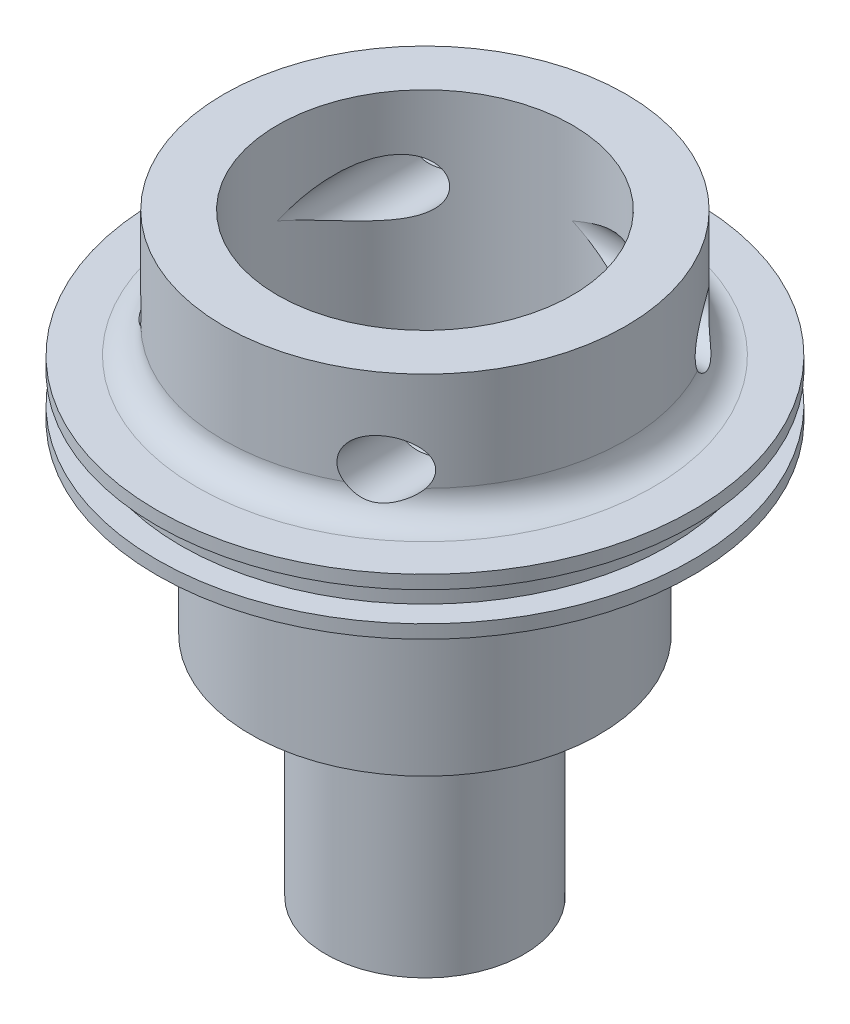
SolidWorks part; units mm, degrees
material "AISI 316 Stainless Steel Sheet (SS)"
ref_plane "Front Plane" through (0, 0, 0) normal (0, 0, 1) x (1, 0, 0)
ref_plane "Top Plane" through (0, 0, 0) normal (0, 1, 0) x (1, 0, 0)
ref_plane "Right Plane" through (0, 0, 0) normal (1, 0, 0) x (0, 0, -1)
ref_axis "Center Axis" through (0, 67.055, 0) along (0, -1, 0)
sketch "Sketch1" plane through (0, 0, 0) normal (0, 1, 0) x (1, 0, 0)
  line L0 (0, 38.4864) -> (0, -44.7335) construction
  line L1 (-72.9011, 0) -> (68.4389, 0) construction
  circle A0 centre (0, 0) radius 32.385
  dimension "D1" = 64.77
extrude "Steel Cylinder" add sketch "Sketch1" along normal blind 56.388
sketch "Sketch3" plane through (0, 0, 0) normal (0, -1, 0) x (1, 0, 0)
  circle A0 centre (0, 0) radius 32.385
  circle A1 centre (0, 0) radius 25.4
  dimension "D1" = 50.8
  dimension "D2" = 64.77
extrude "Bottom Cut Big" cut sketch "Sketch3" against normal blind 44.45
sketch "Sketch2" plane through (0, 0, 0) normal (0, -1, 0) x (1, 0, 0)
  line L0 (0, 55.3519) -> (0, -63.4522) construction
  line L1 (-131.2438, 0) -> (148.0229, 0) construction
  circle A0 centre (0, 0) radius 25.4
  circle A1 centre (0, 0) radius 9.398
  dimension "D1" = 18.796
  dimension "D2" = 50.8
extrude "Bottom Cut Stem" cut sketch "Sketch2" against normal blind 21.59
sketch "Sketch4" plane through (0, 56.388, 0) normal (0, 1, 0) x (1, 0, 0)
  circle A0 centre (0, 0) radius 32.385
  circle A1 centre (0, 0) radius 19.05
  dimension "D1" = 64.77
  dimension "D2" = 38.1
extrude "Top Cut" cut sketch "Sketch4" against normal blind 11.938
sketch "Sketch5" plane through (0, 0, 0) normal (0, -1, 0) x (1, 0, 0)
  circle A0 centre (0, 0) radius 6.35
  dimension "D1" = 12.7
extrude "Stem Inner" cut sketch "Sketch5" against normal up to next
sketch "Sketch6" plane through (0, 56.388, 0) normal (0, 1, 0) x (1, 0, 0)
  circle A0 centre (0, 0) radius 13.97
  dimension "D1" = 27.94
extrude "Top Inner" cut sketch "Sketch6" against normal blind 27.178
sketch "Sketch7" plane through (0, 0, 0) normal (0, 0, 1) x (1, 0, 0)
  line L0 (0, -9.4062) -> (0, 63.414) construction
  line L1 (-55.4601, 0) -> (72.1545, 0) construction
  line L2 (25.4, 40.386) -> (23.114, 40.386)
  line L3 (25.4, 21.59) -> (25.4, 44.45) construction
  line L4 (23.114, 40.386) -> (23.114, 43.18)
  line L5 (23.114, 43.18) -> (25.4, 43.18)
  line L6 (25.4, 44.45) -> (-25.4, 44.45) construction
  line L8 (25.4, 43.18) -> (25.4, 40.386)
  dimension "D1" = 1.27
  dimension "D2" = 2.794
  dimension "D3" = 2.286
revolve "O Ring" cut sketch "Sketch7" angle 360 about axis through (0, 67.055, 0) along (0, -1, 0)
fillet "Top Fillet" radius 2.5654 1 edges at (0, 44.45, 19.05)
sketch "Sketch8" plane through (0, 0, 0) normal (0, 0, 1) x (1, 0, 0)
  line L0 (25.4, 21.59) -> (25.4, 40.386) construction
  line L1 (25.4, 39.116) -> (23.114, 39.116)
  line L2 (25.4, 39.116) -> (25.4, 21.59)
  line L3 (25.4, 21.59) -> (23.114, 21.59)
  line L4 (23.114, 39.116) -> (23.114, 21.59)
  line L5 (25.4, 40.386) -> (-25.4, 40.386) construction
  line L6 (-25.4, 21.59) -> (25.4, 21.59) construction
  dimension "D1" = 1.27
  dimension "D3" = 2.286
revolve "Based O Ring Cut" cut sketch "Sketch8" angle 360 about axis through (0, 67.055, 0) along (0, -1, 0)
sketch "Sketch10" plane through (0, 0, 0) normal (0, 0, 1) x (1, 0, 0)
  line L0 (0, 65.5376) -> (0, -17.6262) construction
  line L1 (13.97, 65.5376) -> (13.97, -17.6262) construction
  line L3 (13.97, 56.388) -> (-13.97, 56.388) construction
  circle A0 centre (11.303, 48.514) radius 2.667
  dimension "D2" = 5.334
  dimension "D1" = 13.97
  dimension "D3" = 7.874
extrude "Intlet Hole" cut sketch "Sketch10" along normal up to next
pattern_circular "Inlet Pattern" count 4 over 360 about axis through (0, 67.055, 0) along (0, -1, 0) of "Intlet Hole"
chamfer "Inner Chamfer" distance 7.62 angle 45 1 edges at (0, 29.21, 6.35)
sketch "Sketch11" plane through (0, 21.59, 0) normal (0, -1, 0) x (1, 0, 0)
  circle A0 centre (0, 0) radius 23.114
  circle A1 centre (0, 0) radius 16.51
  dimension "D1" = 46.228
  dimension "D2" = 33.02
extrude "Middle Outer Cut 2" cut sketch "Sketch11" against normal blind 16.002
sketch "Sketch12" plane through (0, 0, 0) normal (0, 0, 1) x (1, 0, 0)
  line L0 (0, 67.033) -> (0, -16.8211) construction
  line L1 (-16.0044, 21.59) -> (25.074, 21.59) construction
  line L2 (-16.51, 21.59) -> (16.51, 21.59) construction
